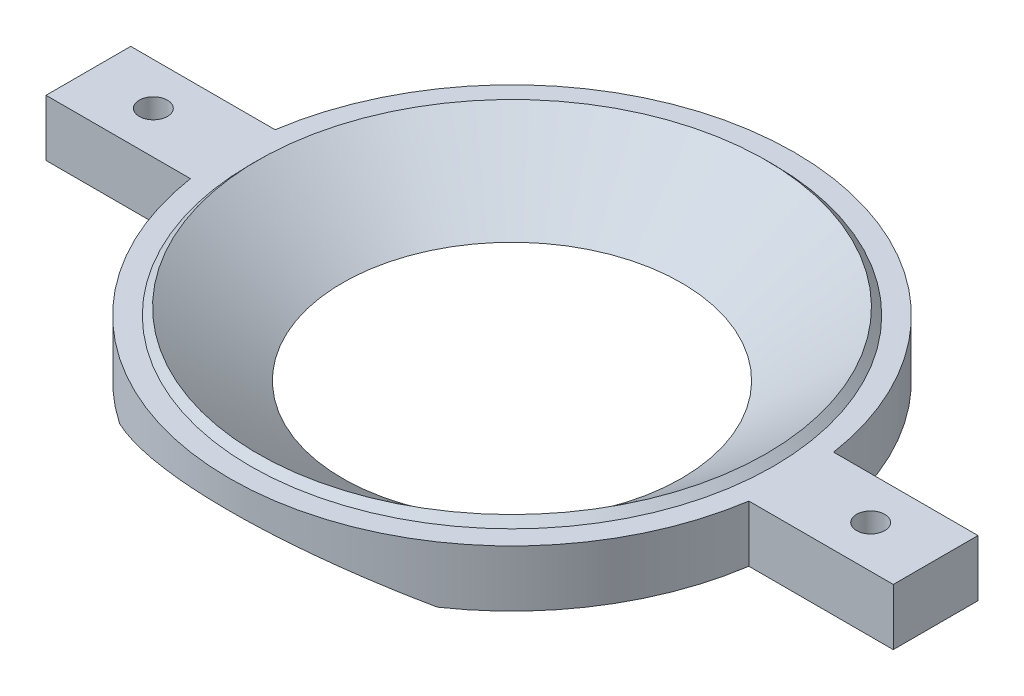
SolidWorks part; units mm, degrees
material "AISI Type 316L stainless steel"
ref_plane "Front Plane" through (0, 0, 0) normal (0, 0, 1) x (1, 0, 0)
ref_plane "Top Plane" through (0, 0, 0) normal (0, 1, 0) x (1, 0, 0)
ref_plane "Right Plane" through (0, 0, 0) normal (1, 0, 0) x (0, 0, -1)
sketch "Sketch1" plane through (0, 0, 0) normal (0, 1, 0) x (1, 0, 0)
  line L0 (0, -1000) -> (0, 49000) construction
  line L1 (-15, -1.5) -> (15, -1.5)
  line L2 (-15, -1.5) -> (-15, 1.5)
  line L3 (-15, 1.5) -> (15, 1.5)
  line L4 (15, -1.5) -> (15, 1.5)
  circle A0 centre (0, 0) radius 10
  circle A1 centre (0, 0) radius 9
  circle A2 centre (-12.7, 0) radius 0.5
  circle A4 centre (12.7, 0) radius 0.5
  point P4 (0, 1.5)
  point P6 (-15, 0)
  dimension "D3" = 20
  dimension "D4" = 1
  dimension "D5" = 1
  dimension "D6" = 12.7
  dimension "D1" = 30
  dimension "D2" = 3
extrude "Boss-Extrude1" add sketch "Sketch1" along normal mid plane 2 contours A0 L3 L2 L1 A2 | A1 L3 A0 L1 | A0 L0 A1 L1 | A1 L0 A0 L3 | L0 A0 L1 A1 | L0 A1 L3 A0 | A0 L1 L4 L3 A4 | A1 L1 A0 L3 region at (-6.4342, 0, 7.484) region at (0.1304, 0, 9.5) region at (-9.4601, 0, 0) region at (-12.4434, 0, 1.4407) region at (10.0308, 0, 0.7566) region at (9.4601, 0, 0) region at (-6.4342, 0, -7.484) region at (6.4342, 0, -7.484)
sketch "Sketch5" plane through (0, 0, 0) normal (0, 0, 1) x (1, 0, 0)
  line L0 (0, -1000) -> (0, 49000) construction
  line L1 (-9.2568, 1) -> (-9, 1.2568)
  line L3 (-9.2568, 1) -> (-9.2568, -1)
  line L4 (-9.2568, -1) -> (-8, -1)
  line L6 (-6, -1) -> (-9.2568, -1)
  line L7 (-9.2568, 1) -> (-9.2568, -1)
  line L8 (-6, -1) -> (-8, -1)
  line L9 (-9, 1.2568) -> (-6, -1)
  spline S0 degree 2 poles (-9, 1.2568) (-7.8451, -0.8984) (-5.9301, -1.0046) knots 0 0 0 1 1 1
  point P7 (-9.2568, 0)
  dimension "D6" = 4
  dimension "D1" = 2
  dimension "D2" = 9
  dimension "D3" = 135
  dimension "D4" = 6
  dimension "D5" = 0.3632
  dimension "D7" = 3.3267
revolve "Revolve1" add sketch "Sketch5" angle 360 about L0 region at (-8.4325, -0.2681, 0) region at (-7.5732, -0.0691, 0)
sketch "Sketch6" plane through (0, 0, 0) normal (1, 0, 0) x (0, 0, -1)
  line L0 (10, 0) -> (10, -1)
  line L1 (10, -1) -> (10, 1) construction
  line L2 (10, -1) -> (8.2679, -1)
  line L3 (1.5, -1) -> (10, -1) construction
  line L4 (8.2679, -1) -> (10, 0)
  line L5 (0, -1000) -> (0, 49000) construction
  line L6 (-10, 0) -> (-10, -1)
  line L7 (-10, -1) -> (-8.2679, -1)
  line L8 (-8.2679, -1) -> (-10, 0)
  dimension "D1" = 60
extrude "Cut-Extrude1" cut sketch "Sketch6" along normal up to surface (15 mm away) from surface up to face at (15, 0, 0) starting at face at (-15, 0, 0)
